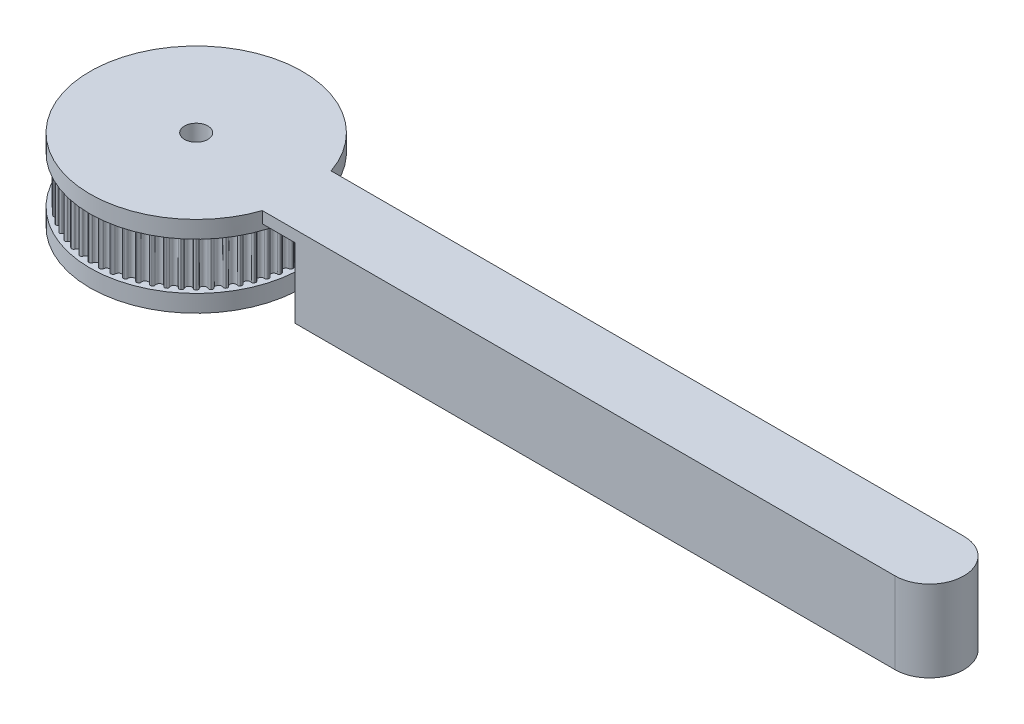
SolidWorks part; units mm, degrees
ref_plane "Front Plane" through (0, 0, 0) normal (0, 0, 1) x (1, 0, 0)
ref_plane "Top Plane" through (0, 0, 0) normal (0, 1, 0) x (1, 0, 0)
ref_plane "Right Plane" through (0, 0, 0) normal (1, 0, 0) x (0, 0, -1)
sketch "Sketch1" plane through (0, 0, 0) normal (0, 1, 0) x (1, 0, 0)
  line L0 (0, 0) -> (0, 28.2667) construction
  line L1 (0, 0) -> (2.9202, 27.7837) construction
  circle A0 centre (0, 0) radius 28.2667 construction
  circle A1 centre (0, 0) radius 27.0467 construction
  circle A2 centre (0, 27.9367) radius 0.89 construction
  circle A5 centre (2.9202, 27.7837) radius 0.89 construction
  arc A6 (0, 27.0467) -> (0.8804, 27.8061) centre (0, 27.9367) ccw
  arc A7 (0.8804, 27.8061) -> (1.3997, 28.2321) centre (1.3749, 27.7327) cw
  arc A8 (1.559, 28.2237) -> (2.031, 27.7458) centre (1.5314, 27.7245) cw
  arc A9 (2.8272, 26.8986) -> (2.031, 27.7458) centre (2.9202, 27.7837) cw
  arc A10 (1.3997, 28.2321) -> (1.559, 28.2237) centre (0, 0) cw
  arc A11 (0, 27.0467) -> (2.8272, 26.8986) centre (0, 0) ccw
  dimension "D1" = 56.5335
  dimension "D3" = 1.78
  dimension "D4" = 0.5
  dimension "D2" = 1.22
  dimension "D5" = 6
extrude "Boss-Extrude1" add sketch "Sketch1" along normal mid plane 13 contours A6 A11 A9 A8 A7 region at (0.001, 0, -0.0192)
ref_axis "Axis1" through (0, 3.3, 0) along (0, -1, 0)
pattern_circular "CirPattern1" count 60 over 360 about axis through (0, 3.3, 0) along (0, -1, 0) of "Boss-Extrude1"
sketch "Sketch2" plane through (0, 0, 0) normal (1, 0, 0) x (0, 0, -1)
  line L10 (0, 6.5) -> (29.4415, 6.5) construction
  line L11 (0, 6.5) -> (0, 8.0875) construction
  line L12 (0, 8.0875) -> (29.4415, 8.0875) construction
  line L15 (29.4415, 6.5) -> (29.4415, 8.0875) construction
  line L20 (0, 3.3) -> (0, -3.3) construction
  line L22 (29.4415, 8.0875) -> (0, 8.0875)
  line L23 (29.4415, 8.0875) -> (29.4415, 6.5)
  line L24 (29.4415, 6.5) -> (0, 6.5)
  line L25 (0, 8.0875) -> (0, 6.5)
  dimension "D1" = 1.5875
  dimension "D2" = 29.4415
  dimension "D3" = 6.5
revolve "Revolve3" add sketch "Sketch2" angle 360 about axis through (0, 3.3, 0) along (0, -1, 0) region at (0, 7.2937, -14.7207)
mirror "Mirror1" about plane through (0, 0, 0) normal (0, 1, 0) of "Revolve3"
sketch "Sketch7" plane through (0, 8.0875, 0) normal (0, 1, 0) x (1, 0, 0)
  line L0 (0, 0) -> (203.2, 0) construction
  line L1 (27.8581, 9.525) -> (203.2, 9.525)
  line L2 (27.8581, -9.525) -> (203.2, -9.525)
  arc A1 (203.2, -9.525) -> (203.2, 9.525) centre (203.2, 0) ccw
  arc A2 (27.8581, 9.525) -> (27.8581, -9.525) centre (0, 0) ccw
  circle A3 centre (0, 0) radius 29.4415 construction
  point P3 (101.6, 0)
  dimension "D1" = 203.2
  dimension "D2" = 19.05
extrude "Boss-Extrude4" add sketch "Sketch7" along normal blind 3.175
sketch "Sketch8" plane through (0, -8.0875, 0) normal (0, -1, 0) x (1, 0, 0)
  circle A0 centre (0, 0) radius 29.4415
  circle A1 centre (0, 0) radius 29.4415 construction
extrude "Boss-Extrude5" add sketch "Sketch8" along normal blind 3.175
sketch "Sketch9" plane through (0, -11.2625, 0) normal (0, -1, 0) x (1, 0, 0)
  circle A0 centre (0, 0) radius 3.2385
  dimension "D1" = 6.477
extrude "Cut-Extrude1" cut sketch "Sketch9" against normal through all both and the other way through all
sketch "Sketch10" plane through (0, 8.0875, 0) normal (0, -1, 0) x (1, 0, 0)
  line L2 (203.2, 9.525) -> (27.8581, 9.525)
  line L3 (27.8581, -9.525) -> (203.2, -9.525)
  line L4 (203.2, 9.525) -> (36.8902, 9.525)
  line L5 (36.8902, -9.525) -> (203.2, -9.525)
  arc A0 (36.8902, 9.525) -> (36.8902, -9.525) centre (0, 0) cw
  arc A2 (27.8581, -9.525) -> (27.8581, 9.525) centre (0, 0) ccw
  arc A3 (203.2, -9.525) -> (203.2, 9.525) centre (203.2, 0) ccw
  arc A5 (203.2, -9.525) -> (203.2, 9.525) centre (203.2, 0) ccw
  dimension "D2" = 38.1
  dimension "D1" = 0
extrude "Boss-Extrude6" add sketch "Sketch10" along normal up to surface (19.35 mm away) up to face at (0, -11.2625, -3.2385)
equation "\"TEETH_NUM\"= 60"
equation "\"TOOTH_PITCH\"= 3mm"
equation "\"PITCH_LINE_OFFSET\"= .015in"
equation "\"DIAMETER_PER_GROOVE\"= \"OUTSIDE_DIAMETER\" / \"TEETH_NUM\" * 1in"
equation "\"PITCH_DIAMETER\"= ( ( \"TEETH_NUM\" * 3 - 1.31 ) / 3.1415 + .415 ) * 1mm"
equation "\"OUTSIDE_DIAMETER\"= \"PITCH_DIAMETER\" - \"PITCH_LINE_OFFSET\" * 2"
equation "\"D1@Sketch1\"=\"OUTSIDE_DIAMETER\""
equation "\"TOOTH_HEIGHT\"= 1.22mm"
equation "\"D2@Sketch1\"=\"TOOTH_HEIGHT\""
equation "\"TOOTH_DIAMETER\"= 1.78mm"
equation "\"INTERNAL_RADIUS\"= .5mm"
equation "\"D3@Sketch1\"=\"TOOTH_DIAMETER\""
equation "\"D5@Sketch1\"=360 / \"TEETH_NUM\""
equation "\"D4@Sketch1\"=\"INTERNAL_RADIUS\""
equation "\"D1@CirPattern1\"=\"TEETH_NUM\""
equation "\"BELT_GAP\"= 13mm"
equation "\"D2@Sketch2\"=\"PITCH_DIAMETER\"/2+1/32"
equation "\"D3@Sketch2\"=\"BELT_GAP\"/2"
equation "\"D1@Boss-Extrude1\"=\"BELT_GAP\""
